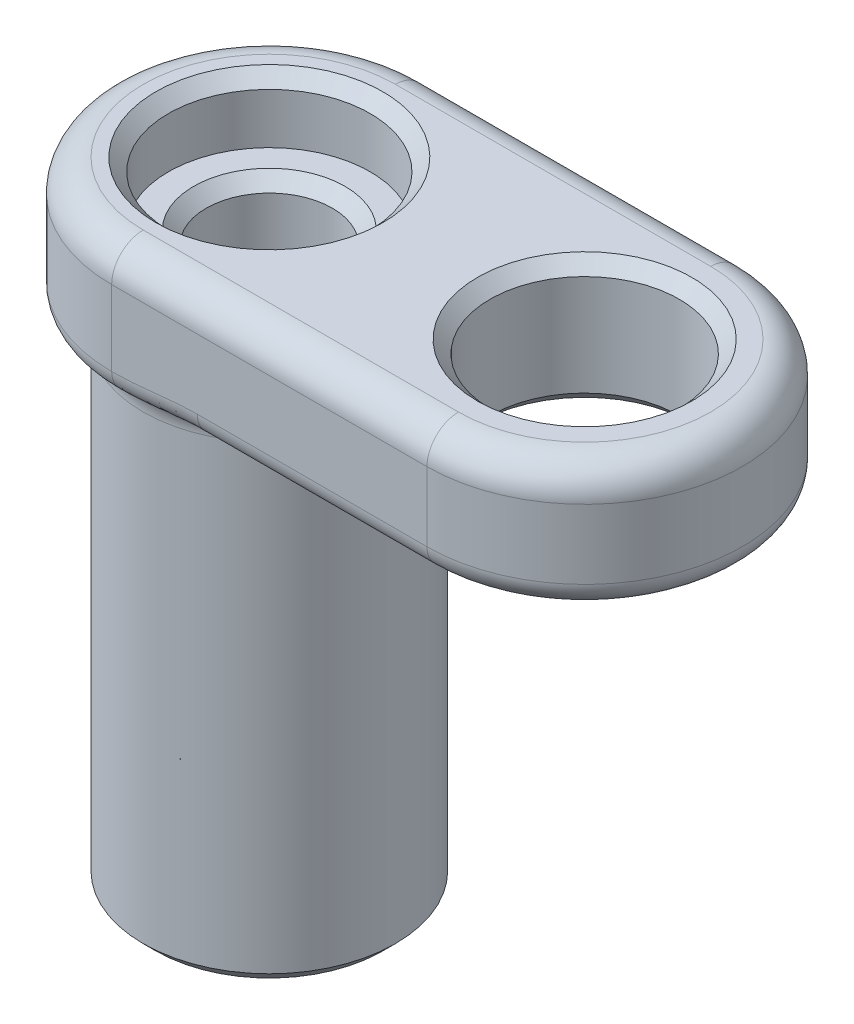
SolidWorks part; units mm, degrees
ref_plane "Front Plane" through (0, 0, 0) normal (0, 0, 1) x (1, 0, 0)
ref_plane "Top Plane" through (0, 0, 0) normal (0, 1, 0) x (1, 0, 0)
ref_plane "Right Plane" through (0, 0, 0) normal (1, 0, 0) x (0, 0, -1)
sketch "Sketch1" plane through (0, 0, 0) normal (0, 1, 0) x (1, 0, 0)
  line L0 (0, 0) -> (50, 0) construction
  line L1 (0, 25) -> (50, 25)
  line L2 (0, -25) -> (50, -25)
  arc A0 (0, 25) -> (0, -25) centre (0, 0) ccw
  arc A1 (50, -25) -> (50, 25) centre (50, 0) ccw
  circle A4 centre (0, 0) radius 20
  point P3 (25, 0)
  dimension "D1" = 25
  dimension "D3" = 40
  dimension "D2" = 50
extrude "Boss-Extrude1" add sketch "Sketch1" along normal blind 20 contours L2 A1 L1 A0 A4 | A4 | A4 | L2 A1 L1 A0 region at (34.7965, 0, 0) region at (0, 0, 0)
extrude "Boss-Extrude2" add sketch "Sketch1<3>" against normal blind 80 contours A4 region at (0, 0, 0)
sketch "Sketch1<3>" plane through (0, 0, 0) normal (0, 1, 0) x (1, 0, 0) same geometry as "Sketch1"
sketch "Sketch4" plane through (0, 20, 0) normal (0, 1, 0) x (1, 0, 0)
  point P0 (0, 0)
hole_wizard "CBORE for M20 Hex Socket Head Cap Screw1" positions "Sketch4" profile "Sketch5" counterbore size "M20" standard "DIN"
sketch "Sketch5" plane through (0, 20, 0) normal (1, 0, 0) x (0, 0, 1)
  line L0 (0, 0) -> (0, 106.0086)
  line L1 (0, 106.0086) -> (10, 100)
  line L2 (10, 100) -> (10, 10)
  line L3 (10, 10) -> (16, 10)
  line L4 (16, 10) -> (16, 0)
  line L5 (16, 0) -> (0, 0)
  line L10 (0, 106.0086) -> (-10, 100) construction
  line L11 (0, -6.35) -> (0, 107.95) construction
  dimension "Hole Dia." = 20
  dimension "Hole Depth" = 100
  dimension "C'Bore Dia." = 32
  dimension "C'Bore Depth" = 10
  dimension "Drill Angle" = 118
sketch "Sketch10" plane through (0, 20, 0) normal (0, 1, 0) x (1, 0, 0)
  point P0 (50, 0)
hole_wizard "Ø1.0mm Dowel Hole1" positions "Sketch10" profile "Sketch11" hole size "Ø1.0" standard "DIN"
sketch "Sketch11" plane through (50, 20, 0) normal (1, 0, 0) x (0, 0, 1)
  line L0 (0, 0) -> (0, 29.0129)
  line L1 (0, 29.0129) -> (15, 20)
  line L2 (15, 20) -> (15, 0)
  line L5 (15, 0) -> (0, 0)
  line L10 (0, 29.0129) -> (-15, 20) construction
  line L11 (0, -6.35) -> (0, 107.95) construction
  dimension "Hole Dia." = 30
  dimension "Hole Depth" = 20
  dimension "Drill Angle" = 118
chamfer "Chamfer1" distance 2 angle 45 6 edges at (50, 20, 15) (50, 0, 15) (0, -80, 10) (0, 10, 10) (0, 20, 16) (0, -80, 20)
fillet "Fillet1" radius 5 5 edges at (-25, 20, 0) (25, 20, -25) (75, 20, 0) (0, 0, 20) (25, 20, 25)
fillet "Fillet2" radius 4 4 edges at (25, 0, 25) (-25, 0, 0) (25, 0, -25) (75, 0, 0)
